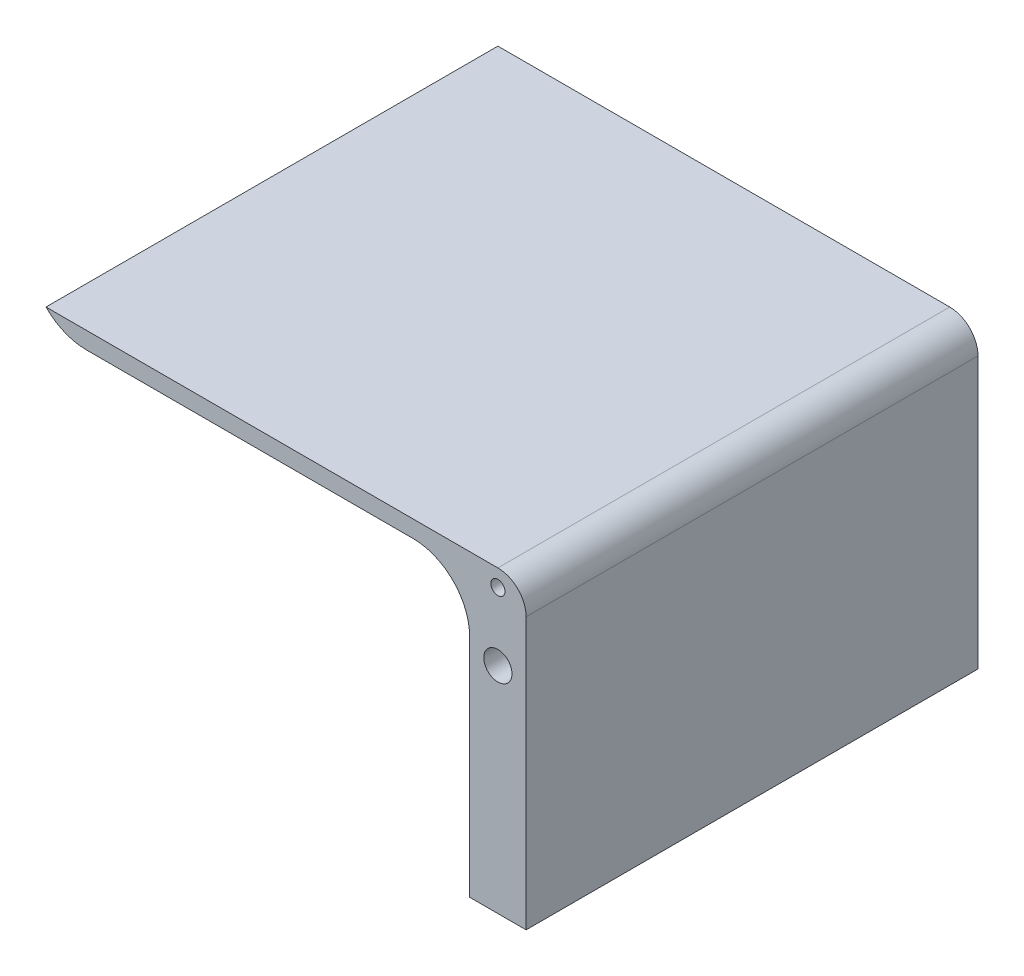
SolidWorks part; units mm, degrees
ref_plane "Plano frontal" through (0, 0, 0) normal (0, 0, 1) x (1, 0, 0)
ref_plane "Plano superior" through (0, 0, 0) normal (0, 1, 0) x (1, 0, 0)
ref_plane "Plano direito" through (0, 0, 0) normal (1, 0, 0) x (0, 0, -1)
sketch "Esboço1" plane through (0, 0, 0) normal (0, 0, 1) x (1, 0, 0)
  line L1 (-78.6982, 27.7414) -> (6.3018, 27.7414)
  line L2 (-78.6982, 27.7414) -> (-78.6982, 24.7414)
  line L3 (-78.6982, 24.7414) -> (-3.6982, 24.7414)
  line L4 (6.3018, 27.7414) -> (6.3018, 24.7414)
  line L6 (-3.6982, 24.7414) -> (-3.6982, -25.2586)
  line L7 (-3.6982, -25.2586) -> (6.3018, -25.2586)
  line L8 (6.3018, 24.7414) -> (6.3018, -25.2586)
  dimension "D1" = 3
  dimension "D2" = 10
  dimension "D3" = 50
  dimension "D4" = 85
extrude "Ressalto-extrusão1" add sketch "Esboço1" along normal blind 80
sketch "Esboço3" plane through (0, 0, 80) normal (0, 0, 1) x (1, 0, 0)
  line L0 (6.3018, -25.2586) -> (6.3018, 27.7414) construction
  line L2 (6.3018, 27.7414) -> (-78.6982, 27.7414) construction
  circle A0 centre (1.3018, 12.7414) radius 2.5
  dimension "D1" = 5
  dimension "D2" = 5
  dimension "D3" = 15
extrude "Corte-extrusão2" cut sketch "Esboço3" against normal blind 10
sketch "Esboço4" plane through (0, 0, 80) normal (0, 0, 1) x (1, 0, 0)
  line L0 (6.3018, -25.2586) -> (6.3018, 27.7414) construction
  line L2 (6.3018, 27.7414) -> (-78.6982, 27.7414) construction
  circle A0 centre (1.3018, 24.7414) radius 1.25
  dimension "D1" = 2.5
  dimension "D2" = 5
  dimension "D3" = 3
extrude "Corte-extrusão3" cut sketch "Esboço4" against normal blind 10
fillet "Filete1" radius 10 1 edges at (-3.6982, 24.7414, 40)
fillet "Filete2" radius 5 1 edges at (6.3018, 27.7414, 40)
fillet "Filete3" radius 10 1 edges at (-78.6982, 24.7414, 40)
